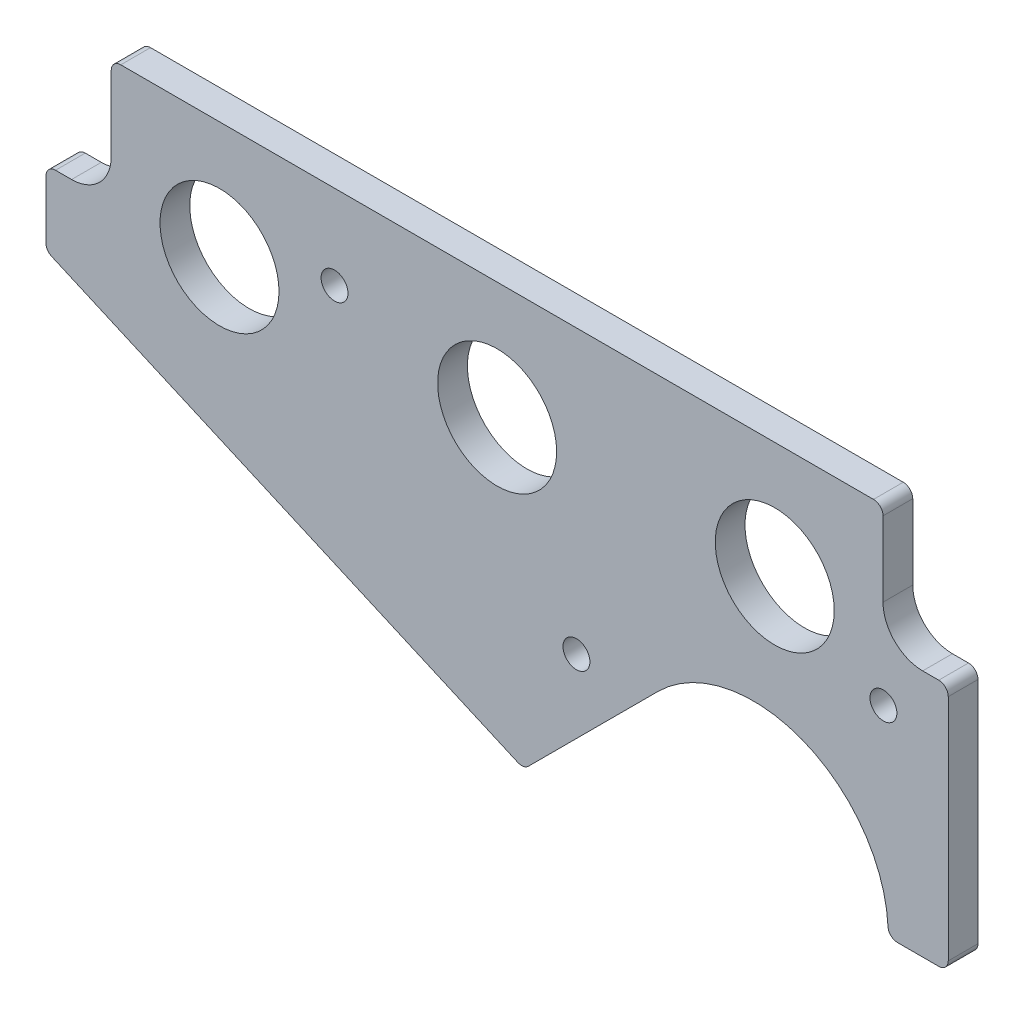
SolidWorks part; units mm, degrees
ref_plane "Front Plane" through (0, 0, 0) normal (0, 0, 1) x (1, 0, 0)
ref_plane "Top Plane" through (0, 0, 0) normal (0, 1, 0) x (1, 0, 0)
ref_plane "Right Plane" through (0, 0, 0) normal (1, 0, 0) x (0, 0, -1)
sketch "Sketch1" plane through (0, 0, -34.4312) normal (0, 0, 1) x (1, 0, 0)
  line L20 (-842.1271, 5946.1063) -> (-962.6501, 5946.1063)
  line L21 (-964.1741, 5944.5823) -> (-964.1741, 5932.6125)
  line L22 (-970.5241, 5926.2625) -> (-973.0958, 5926.2625)
  line L23 (-974.6198, 5924.7385) -> (-974.6198, 5915.3924)
  line L24 (-973.7096, 5913.9975) -> (-899.0731, 5881.1574)
  line L25 (-897.3817, 5881.4747) -> (-876.634, 5902.2225)
  line L26 (-838.2818, 5886.575) -> (-831.6813, 5886.575)
  line L27 (-830.1573, 5888.099) -> (-830.1573, 5924.7385)
  line L28 (-831.6813, 5926.2625) -> (-834.2531, 5926.2625)
  line L29 (-840.6031, 5932.6125) -> (-840.6031, 5944.5823)
  line L30 (-842.1271, 5946.1063) -> (-962.6501, 5946.1063)
  line L31 (-964.1741, 5944.5823) -> (-964.1741, 5932.6125)
  line L32 (-970.5241, 5926.2625) -> (-973.0958, 5926.2625)
  line L33 (-974.6198, 5924.7385) -> (-974.6198, 5915.3924)
  line L34 (-973.7096, 5913.9975) -> (-899.0731, 5881.1574)
  line L35 (-897.3817, 5881.4747) -> (-876.634, 5902.2225)
  line L36 (-838.2818, 5886.575) -> (-831.6813, 5886.575)
  line L37 (-830.1573, 5888.099) -> (-830.1573, 5924.7385)
  line L38 (-831.6813, 5926.2625) -> (-834.2531, 5926.2625)
  line L39 (-840.6031, 5932.6125) -> (-840.6031, 5944.5823)
  arc A22 (-840.6031, 5944.5823) -> (-842.1271, 5946.1063) centre (-842.1271, 5944.5823) ccw
  arc A23 (-962.6501, 5946.1063) -> (-964.1741, 5944.5823) centre (-962.6501, 5944.5823) ccw
  arc A24 (-970.5241, 5926.2625) -> (-964.1741, 5932.6125) centre (-970.5241, 5932.6125) ccw
  arc A25 (-973.0958, 5926.2625) -> (-974.6198, 5924.7385) centre (-973.0958, 5924.7385) ccw
  arc A26 (-974.6198, 5915.3924) -> (-973.7096, 5913.9975) centre (-973.0958, 5915.3924) ccw
  arc A27 (-899.0731, 5881.1574) -> (-897.3817, 5881.4747) centre (-898.4594, 5882.5524) ccw
  arc A28 (-839.804, 5888.0237) -> (-876.634, 5902.2225) centre (-861.3676, 5886.956) ccw
  arc A29 (-839.804, 5888.0237) -> (-838.2818, 5886.575) centre (-838.2818, 5888.099) ccw
  arc A30 (-831.6813, 5886.575) -> (-830.1573, 5888.099) centre (-831.6813, 5888.099) ccw
  arc A31 (-830.1573, 5924.7385) -> (-831.6813, 5926.2625) centre (-831.6813, 5924.7385) ccw
  arc A32 (-840.6031, 5932.6125) -> (-834.2531, 5926.2625) centre (-834.2531, 5932.6125) ccw
  arc A33 (-840.6031, 5944.5823) -> (-842.1271, 5946.1063) centre (-842.1271, 5944.5823) ccw
  arc A34 (-962.6501, 5946.1063) -> (-964.1741, 5944.5823) centre (-962.6501, 5944.5823) ccw
  arc A35 (-970.5241, 5926.2625) -> (-964.1741, 5932.6125) centre (-970.5241, 5932.6125) ccw
  arc A36 (-973.0958, 5926.2625) -> (-974.6198, 5924.7385) centre (-973.0958, 5924.7385) ccw
  arc A37 (-974.6198, 5915.3924) -> (-973.7096, 5913.9975) centre (-973.0958, 5915.3924) ccw
  arc A38 (-899.0731, 5881.1574) -> (-897.3817, 5881.4747) centre (-898.4594, 5882.5524) ccw
  arc A39 (-839.804, 5888.0237) -> (-876.634, 5902.2225) centre (-861.3676, 5886.956) ccw
  arc A40 (-839.804, 5888.0237) -> (-838.2818, 5886.575) centre (-838.2818, 5888.099) ccw
  arc A41 (-831.6813, 5886.575) -> (-830.1573, 5888.099) centre (-831.6813, 5888.099) ccw
  arc A42 (-830.1573, 5924.7385) -> (-831.6813, 5926.2625) centre (-831.6813, 5924.7385) ccw
  arc A43 (-840.6031, 5932.6125) -> (-834.2531, 5926.2625) centre (-834.2531, 5932.6125) ccw
  dimension "D1" = 0
extrude "Boss-Extrude1" add sketch "Sketch1" along normal blind 4.7625
hole_wizard "#6 Clearance Hole1" positions "Sketch4" profile "Sketch3" hole size "#6" standard "ANSI Inch" end condition through all
sketch "Sketch4" plane through (0, 0, -29.6687) normal (0, 0, 1) x (1, 0, 0)
  point P0 (-840.5396, 5918.325)
  point P3 (-889.6886, 5900.8625)
  point P6 (-928.4236, 5932.6125)
sketch "Sketch3" plane through (-840.5396, 5918.325, -29.6687) normal (1, 0, 0) x (0, -1, 0)
  line L0 (0, 0) -> (0, 4.7625)
  line L1 (0, 4.7625) -> (2.1526, 4.7625)
  line L2 (2.1526, 4.7625) -> (2.1526, 0)
  line L5 (2.1526, 0) -> (0, 0)
  line L11 (0, -6.35) -> (0, 107.95) construction
  dimension "Thru Hole Dia." = 4.3053
  dimension "Thru Hole Depth" = 4.7625
sketch "Sketch5" plane through (0, 0, -29.6687) normal (0, 0, 1) x (1, 0, 0)
  circle A0 centre (-857.9386, 5927.5242) radius 9.525
  circle A1 centre (-902.3886, 5927.342) radius 9.525
  circle A2 centre (-946.8386, 5927.342) radius 9.525
  dimension "D1" = 19.05
extrude "Cut-Extrude1" cut sketch "Sketch5" against normal through all
